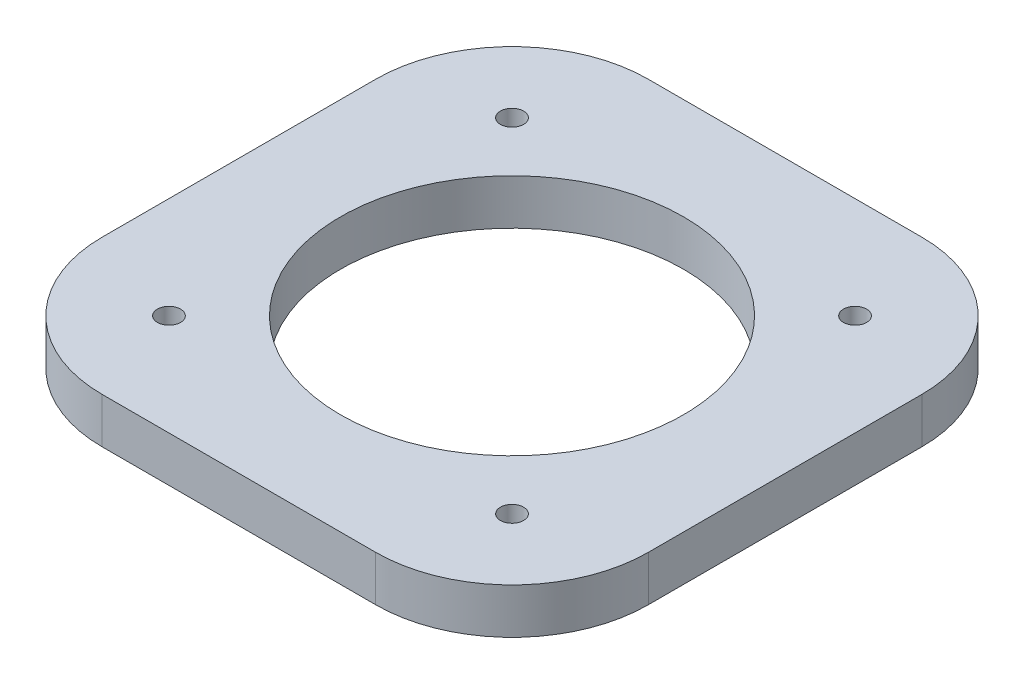
SolidWorks part; units mm, degrees
ref_plane "Front Plane" through (0, 0, 0) normal (0, 0, 1) x (1, 0, 0)
ref_plane "Top Plane" through (0, 0, 0) normal (0, 1, 0) x (1, 0, 0)
ref_plane "Right Plane" through (0, 0, 0) normal (1, 0, 0) x (0, 0, -1)
sketch "Sketch1" plane through (0, 0, 0) normal (0, 1, 0) x (1, 0, 0)
  line L1 (-37.7595, 37.7595) -> (37.7595, 37.7595) construction
  line L2 (-37.7595, 37.7595) -> (-37.7595, -37.7595) construction
  line L3 (-37.7595, -37.7595) -> (37.7595, -37.7595) construction
  line L4 (37.7595, 37.7595) -> (37.7595, -37.7595) construction
  line L5 (-37.7595, 37.7595) -> (37.7595, -37.7595) construction
  line L6 (-37.7595, -37.7595) -> (37.7595, 37.7595) construction
  line L7 (-30.1041, 60.1041) -> (30.1041, 60.1041)
  line L8 (-60.1041, 30.1041) -> (-60.1041, -30.1041)
  line L9 (-30.1041, -60.1041) -> (30.1041, -60.1041)
  line L10 (60.1041, 30.1041) -> (60.1041, -30.1041)
  line L11 (-60.1041, 60.1041) -> (60.1041, -60.1041) construction
  line L12 (-60.1041, -60.1041) -> (60.1041, 60.1041) construction
  circle A0 centre (37.7595, 37.7595) radius 2.55
  circle A1 centre (37.7595, -37.7595) radius 2.55
  circle A2 centre (-37.7595, -37.7595) radius 2.55
  circle A3 centre (-37.7595, 37.7595) radius 2.55
  circle A4 centre (0, 0) radius 37.7595
  arc A5 (-30.1041, -60.1041) -> (-60.1041, -30.1041) centre (-30.1041, -30.1041) cw
  arc A6 (-30.1041, 60.1041) -> (-60.1041, 30.1041) centre (-30.1041, 30.1041) ccw
  arc A7 (30.1041, 60.1041) -> (60.1041, 30.1041) centre (30.1041, 30.1041) cw
  arc A8 (60.1041, -30.1041) -> (30.1041, -60.1041) centre (30.1041, -30.1041) cw
  point P0 (0, 0)
  point P6 (0, 0)
  point P21 (0, 0)
  dimension "D3" = 5.1
  dimension "D5" = 30
  dimension "D1" = 106.8
  dimension "D2" = 170
  dimension "D4" = 4
extrude "Boss-Extrude1" add sketch "Sketch1" along normal blind 10
